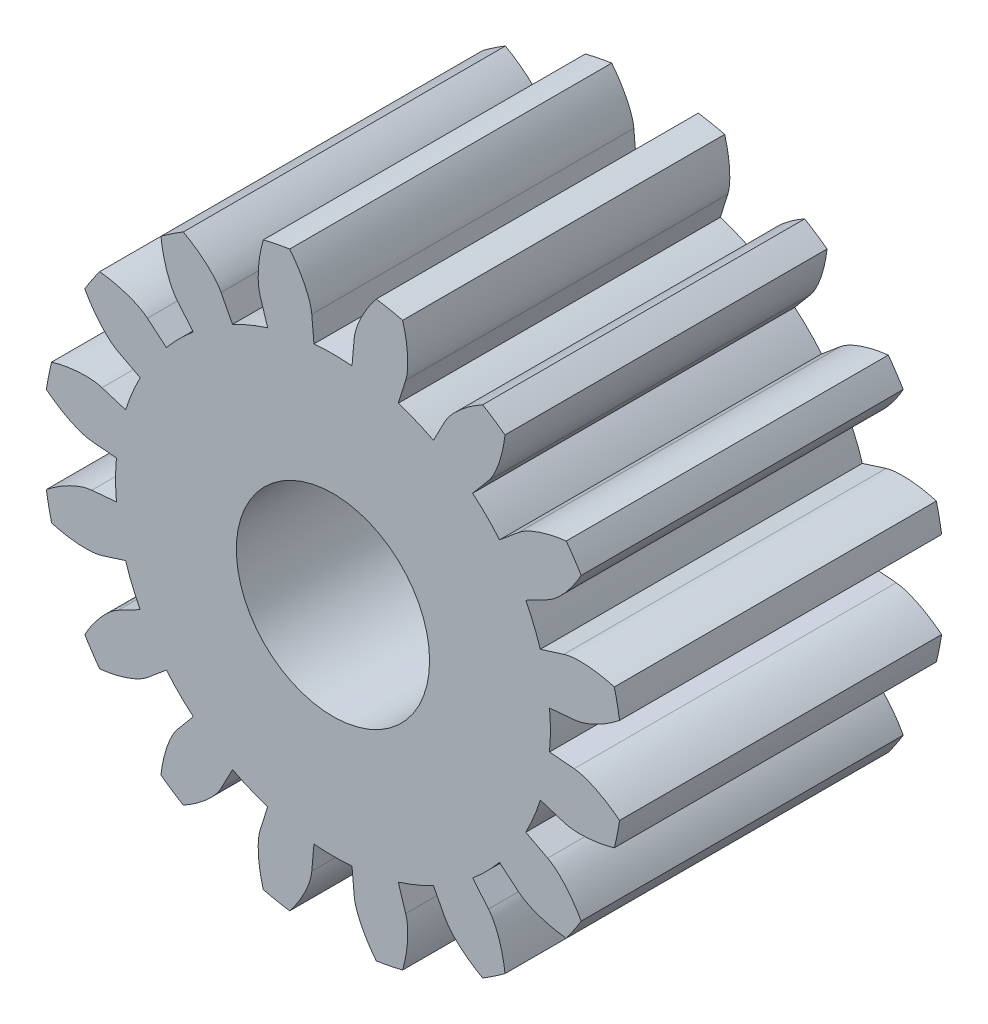
SolidWorks part; units mm, degrees
ref_plane "前视基准面" through (0, 0, 0) normal (0, 0, 1) x (1, 0, 0)
ref_plane "上视基准面" through (0, 0, 0) normal (0, 1, 0) x (1, 0, 0)
ref_plane "右视基准面" through (0, 0, 0) normal (1, 0, 0) x (0, 0, -1)
other "Configuration Table"
sketch "草图1" plane through (0, 0, 0) normal (0, 0, 1) x (1, 0, 0)
  line L0 (0, 0) -> (4, 0) construction
  line L1 (0, 0) -> (3.9807, 0.3921) construction
  line L2 (0, 0) -> (3.7443, 0.3291)
  line L3 (3.9807, 0.3921) -> (3.9807, -0.3921) construction
  line L4 (0, 0) -> (3.7443, -0.3291)
  circle A0 centre (0, 0) radius 4.5
  circle A1 centre (0, 0) radius 4 construction
  circle A2 centre (0, 0) radius 3.375
  circle A3 centre (0, 0) radius 3.7588 construction
  circle A4 centre (0, 0) radius 1.5
  spline S0 degree 4 poles (3.7443, 0.3291) (3.7729, 0.3316) (3.852, 0.3445) (3.9981, 0.3926) (4.2218, 0.5023) (4.4866, 0.6881) (4.7894, 0.9723) (5.0903, 1.3552) (5.3572, 1.8186) (5.6269, 2.4866) (5.7837, 3.1915) (5.8395, 3.939) (5.7839, 4.8292) (5.6145, 5.7064) (5.2709, 6.6864) (4.7256, 7.7028) (4.0402, 8.6299) (3.2362, 9.4556) (2.3338, 10.1718) (1.3511, 10.7732) (0.306, 11.2565) (-0.6502, 11.5751) (-1.4192, 11.7574) (-1.9866, 11.8556) (-2.3401, 11.9048) (-2.6306, 11.9368) (-2.9071, 11.9619) (-3.2112, 11.9792) (-3.4455, 11.9894) (-3.715, 11.9923) (-3.9867, 11.9914) (-4.2588, 11.9836) (-4.7357, 11.9589) (-5.1232, 11.9154) (-5.525, 11.8674) (-5.7188, 11.8311) (-5.8484, 11.8109) knots 0 0 0 0 0 0.005604 0.015718 0.02996 0.048734 0.068727 0.096889 0.125051 0.153212 0.209535 0.237696 0.271429 0.327752 0.384075 0.440398 0.496721 0.553044 0.609367 0.66569 0.722013 0.778336 0.806497 0.820578 0.834659 0.84874 0.86282 0.876901 0.890982 0.900036 0.909091 0.931818 0.954545 0.977273 1 1 1 1 1 construction
  spline S1 degree 4 poles (3.7443, 0.3291) (3.7729, 0.3316) (3.852, 0.3445) (3.9981, 0.3926) (4.2218, 0.5023) (4.4866, 0.6881) (4.7894, 0.9723) (5.0903, 1.3552) (5.3572, 1.8186) (5.6269, 2.4866) (5.7837, 3.1915) (5.8395, 3.939) (5.7839, 4.8292) (5.6145, 5.7064) (5.2709, 6.6864) (4.7256, 7.7028) (4.0402, 8.6299) (3.2362, 9.4556) (2.3338, 10.1718) (1.3511, 10.7732) (0.306, 11.2565) (-0.6502, 11.5751) (-1.4192, 11.7574) (-1.9866, 11.8556) (-2.3401, 11.9048) (-2.6306, 11.9368) (-2.9071, 11.9619) (-3.2112, 11.9792) (-3.4455, 11.9894) (-3.715, 11.9923) (-3.8743, 11.9918) (-3.9585, 11.9906) (-4.0005, 11.9898) knots 0 0 0 0 0 0.005604 0.015718 0.02996 0.048734 0.068727 0.096889 0.125051 0.153212 0.209535 0.237696 0.271429 0.327752 0.384075 0.440398 0.496721 0.553044 0.609367 0.66569 0.722013 0.778336 0.806497 0.820578 0.834659 0.84874 0.86282 0.876901 0.890982 0.900036 0.909091 0.909091 0.909091 0.909091 0.909091
  spline S2 degree 4 poles (3.7443, -0.3291) (3.7729, -0.3316) (3.852, -0.3445) (3.9981, -0.3926) (4.2218, -0.5023) (4.4866, -0.6881) (4.7894, -0.9723) (5.0903, -1.3552) (5.3572, -1.8186) (5.6269, -2.4866) (5.7837, -3.1915) (5.8395, -3.939) (5.7839, -4.8292) (5.6145, -5.7064) (5.2709, -6.6864) (4.7256, -7.7028) (4.0402, -8.6299) (3.2362, -9.4556) (2.3338, -10.1718) (1.3511, -10.7732) (0.306, -11.2565) (-0.6502, -11.5751) (-1.4192, -11.7574) (-1.9866, -11.8556) (-2.3401, -11.9048) (-2.6306, -11.9368) (-2.9071, -11.9619) (-3.2112, -11.9792) (-3.4455, -11.9894) (-3.715, -11.9923) (-3.9867, -11.9914) (-4.2588, -11.9836) (-4.7357, -11.9589) (-5.1232, -11.9154) (-5.525, -11.8674) (-5.7188, -11.8311) (-5.8484, -11.8109) knots 0 0 0 0 0 0.005604 0.015718 0.02996 0.048734 0.068727 0.096889 0.125051 0.153212 0.209535 0.237696 0.271429 0.327752 0.384075 0.440398 0.496721 0.553044 0.609367 0.66569 0.722013 0.778336 0.806497 0.820578 0.834659 0.84874 0.86282 0.876901 0.890982 0.900036 0.909091 0.931818 0.954545 0.977273 1 1 1 1 1 construction
  spline S3 degree 4 poles (3.7443, -0.3291) (3.7729, -0.3316) (3.852, -0.3445) (3.9981, -0.3926) (4.2218, -0.5023) (4.4866, -0.6881) (4.7894, -0.9723) (5.0903, -1.3552) (5.3572, -1.8186) (5.6269, -2.4866) (5.7837, -3.1915) (5.8395, -3.939) (5.7839, -4.8292) (5.6145, -5.7064) (5.2709, -6.6864) (4.7256, -7.7028) (4.0402, -8.6299) (3.2362, -9.4556) (2.3338, -10.1718) (1.3511, -10.7732) (0.306, -11.2565) (-0.6502, -11.5751) (-1.4192, -11.7574) (-1.9866, -11.8556) (-2.3401, -11.9048) (-2.6306, -11.9368) (-2.9071, -11.9619) (-3.2112, -11.9792) (-3.4455, -11.9894) (-3.715, -11.9923) (-3.8743, -11.9918) (-3.9585, -11.9906) (-4.0005, -11.9898) knots 0 0 0 0 0 0.005604 0.015718 0.02996 0.048734 0.068727 0.096889 0.125051 0.153212 0.209535 0.237696 0.271429 0.327752 0.384075 0.440398 0.496721 0.553044 0.609367 0.66569 0.722013 0.778336 0.806497 0.820578 0.834659 0.84874 0.86282 0.876901 0.890982 0.900036 0.909091 0.909091 0.909091 0.909091 0.909091
  point P15 (3.9807, 0)
  dimension "齿顶圆直径" = 9
  dimension "分度圆直径" = 8
  dimension "齿根圆直径" = 6.75
  dimension "基圆直径" = 7.5175
  dimension "内孔直径" = 3
  dimension "渐近线镜像线夹角" = 5.625
extrude "凸台-拉伸1" add sketch "草图1" along normal blind 5 contours A0 | A4
extrude "切除-拉伸1" cut sketch "草图1<3>" along normal through all contours A2 S3 A0 S1 region at (4.0116, 0, 0)
sketch "草图1<3>" plane through (0, 0, 0) normal (0, 0, 1) x (1, 0, 0) same geometry as "草图1"
pattern_circular "阵列(圆周)1" count 16 every 22.5 about axis through (0, 0, 5) along (0, 0, 1) of "切除-拉伸1"
equation "\"m\" = 0.5'模数"
equation "\"z\"= 16'齿数"
equation "\"a\"= 20度'压力角"
equation "\"d\"= \"m\" * \"z\"'分度圆直径"
equation "\"da\"= ( \"z\" + 2 ) * \"m\"'齿顶圆直径"
equation "\"df\"= ( \"z\" - 2.5 ) * \"m\"'齿根圆直径"
equation "\"s\"= 0.5 * PI * \"m\"'分度圆齿厚"
equation "\"r\"= 0.38 * \"m\"'齿根圆角"
equation "\"B\"= 0.3 * \"d\"'齿厚"
equation "\"db\"= \"m\" * \"z\" * cos ( \"a\" )'基圆直径"
equation "\"rb\"= \"db\" / 2'基圆半径"
equation "\"齿顶圆直径@草图1\"= \"da\""
equation "\"分度圆直径@草图1\"= \"d\""
equation "\"齿根圆直径@草图1\"= \"df\""
equation "\"基圆直径@草图1\"= \"db\""
equation "\"渐近线镜像线夹角@草图1\"= 360 / 4 / \"z\""
equation "\"h\"= 5'齿轮厚度"
equation "\"ir\"= 3'内孔直径"
equation "\"内孔直径@草图1\"= \"ir\""
equation "\"齿轮厚@凸台-拉伸1\"= \"h\""
equation "\"齿轮夹角@阵列(圆周)1\"= 360 / \"z\""
equation "\"齿数@阵列(圆周)1\"= \"z\""
